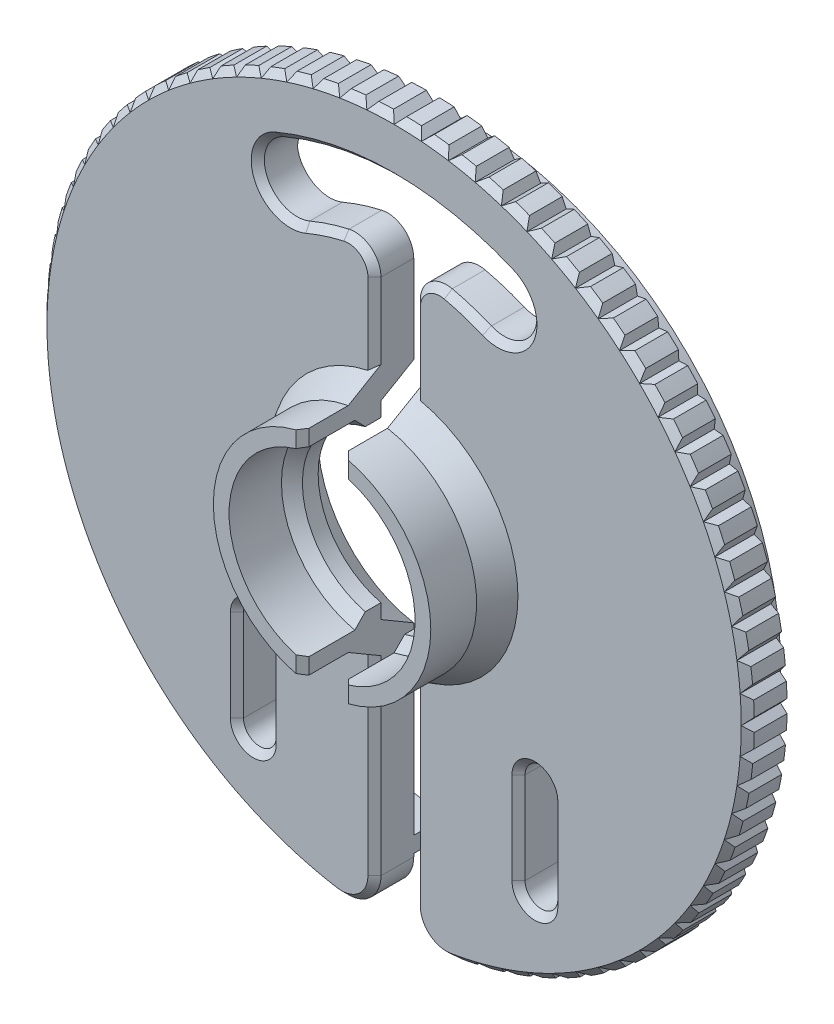
SolidWorks part; units mm, degrees
note: '?' marks a value the reader was unsure of.
ref_plane "Front Plane" through (0, 0, 0) normal (0, 0, 1) x (1, 0, 0)
ref_plane "Top Plane" through (0, 0, 0) normal (0, 1, 0) x (1, 0, 0)
ref_plane "Right Plane" through (0, 0, 0) normal (1, 0, 0) x (0, 0, -1)
sketch "Sketch1" plane through (0, 0, 0) normal (0, 0, 1) x (1, 0, 0)
  circle A0 centre (0, 0) radius 24
  circle A1 centre (0, 0) radius 22.8
  dimension "D1" = 48
  dimension "D2" = 1.2
extrude "coll-lens-ring" add sketch "Sketch1" along normal blind 2.5
ref_axis "Axis1" through (0, 0, 0) along (0, 0, -1)?
sketch "Sketch2" plane through (0, 0, 2.5) normal (0, 0, 1) x (1, 0, 0)
  circle A0 centre (0, 0) radius 27
  circle A1 centre (0, 0) radius 24 construction
  dimension "D1" = 3
extrude "plate" add sketch "Sketch2" along normal blind 3
sketch "Sketch3" plane through (0, 0, 5.5) normal (0, 0, 1) x (1, 0, 0)
  circle A0 centre (0, 0) radius 7.1
  dimension "D1" = 14.2
extrude "lens-hole" cut sketch "Sketch3" against normal through all
sketch "Sketch4" plane through (0, 0, 2.5) normal (0, 0, -1) x (-1, 0, 0)
  circle A0 centre (0, 0) radius 7.1
  circle A1 centre (0, 0) radius 8.3
  circle A2 centre (0, 0) radius 7.1 construction
  dimension "D1" = 1.2
extrude "lens-guide" add sketch "Sketch4" against normal blind 5.5 from surface at -3 starting at face at (7.1, 0, 5.5)
sketch "Sketch5" plane through (0, 0, 11) normal (0, 0, 1) x (1, 0, 0)
  circle A0 centre (0, 0) radius 8.3
  circle A1 centre (0, 0) radius 8.3 construction
  circle A2 centre (0, 0) radius 6.3
  circle A3 centre (0, 0) radius 7.1 construction
  dimension "D1" = 0.8
extrude "lens-stop" add sketch "Sketch5" against normal blind 1 from offset 5 offset against normal yes
chamfer "Chamfer2" distance 2 angle 30 1 edges at (8.3, 0, 5.5)
chamfer "Chamfer3" distance 3 angle 30 1 edges at (7.1, 0, 2.5)
sketch "Sketch6" plane through (0, 0, 2.5) normal (0, 0, -1) x (-1, 0, 0)
  line L0 (0, 0) -> (0, 27) construction
  line L1 (0, 6.05) -> (0, -6.05) construction
  line L2 (-1.5, 6.1188) -> (-1.5, 15.4075)
  line L3 (0, 0) -> (-13.5, 23.3827) construction
  line L4 (-1.5, -26.9583) -> (-1.5, -6.1188)
  line L5 (0, 0) -> (13.5, 23.3827) construction
  line L6 (1.5, -26.9583) -> (1.5, -6.1188)
  line L7 (1.5, 6.1188) -> (1.5, 15.4075)
  circle A0 centre (0, 0) radius 27 construction
  arc A1 (8.8815, 20.999) -> (-8.8815, 20.999) centre (0, 0) ccw
  circle A3 centre (0, 0) radius 6.3 construction
  arc A4 (-6.9338, 16.394) -> (-8.8815, 20.999) centre (-7.9077, 18.6965) cw
  arc A5 (-3.943, 17.3578) -> (-6.9338, 16.394) centre (0, 0) ccw
  arc A6 (-1.5, 15.4075) -> (-3.943, 17.3578) centre (-3.5, 15.4075) ccw
  arc A7 (1.5, 6.1188) -> (-1.5, 6.1188) centre (0, 0) ccw
  arc A8 (-1.5, -6.1188) -> (1.5, -6.1188) centre (0, 0) ccw
  arc A9 (-1.5, -26.9583) -> (1.5, -26.9583) centre (0, 0) ccw
  arc A10 (1.5, 15.4075) -> (3.943, 17.3578) centre (3.5, 15.4075) cw
  arc A11 (3.943, 17.3578) -> (6.9338, 16.394) centre (0, 0) cw
  arc A12 (6.9338, 16.394) -> (8.8815, 20.999) centre (7.9077, 18.6965) ccw
  circle A13 centre (0, 0) radius 22.8 construction
  dimension "D1" = 1.5
  dimension "D2" = 2.5
  dimension "D3" = 2
  dimension "D4" = 30
extrude "flexure-slot" cut sketch "Sketch6" against normal through all both and the other way through all
sketch "Sketch7" plane through (0, 0, 2.5) normal (0, 0, -1) x (-1, 0, 0)
  line L0 (-9.5, -19) -> (-9.5, -12)
  line L1 (-12, -19) -> (-12, -12)
  line L2 (0, 6.05) -> (0, -6.05) construction
  line L3 (12, -19) -> (12, -12)
  line L4 (9.5, -19) -> (9.5, -12)
  arc A0 (-9.5, -19) -> (-12, -19) centre (-10.75, -19) cw
  arc A1 (-12, -12) -> (-9.5, -12) centre (-10.75, -12) cw
  arc A2 (12, -12) -> (9.5, -12) centre (10.75, -12) ccw
  arc A3 (9.5, -19) -> (12, -19) centre (10.75, -19) ccw
  dimension "D1" = 2.5
  dimension "D2" = 7
  dimension "D3" = 9.5
  dimension "D4" = 12
extrude "peg slots" cut sketch "Sketch7" against normal through all
fillet "Fillet1" radius 2 2 edges at (-22.7358, 1.7097, 2.5) (6.1404, -21.9576, 2.5)
fillet "Fillet2" radius 2.5 2 edges at (-1.5, -26.9583, 4) (1.5, -26.9583, 4)
chamfer "Chamfer1" distance 0.5 angle 45 26 edges at (0, 27, 5.5) (-1.5, 12.3712, 5.5) (-2.2522, 16.9705, 5.5) (-5.4597, 16.942, 5.5) (-10.2102, 17.7226, 5.5) (0, 22.8, 5.5) (10.2102, 17.7226, 5.5) (5.4597, 16.942, 5.5) (2.2522, 16.9705, 5.5) (1.5, 12.3712, 5.5) (1.5, -16.7531, 5.5) (-1.5, -16.7531, 5.5) (10.75, -10.75, 5.5) (12, -15.5, 5.5) (9.5, -15.5, 5.5) (10.75, -20.25, 5.5) (-10.75, -10.75, 5.5) (-9.5, -15.5, 5.5) (-12, -15.5, 5.5) (-10.75, -20.25, 5.5) (2.383, -26.0779, 5.5) (-2.383, -26.0779, 5.5) (-1.5, -7.5515, 11) (-1.5, 7.5515, 11) (1.5, -7.5515, 11) (1.5, 7.5515, 11)
chamfer "Chamfer4" distance 1 angle 45 1 edges at (-7.1, 0, 6)
sketch "Sketch8" plane through (0, 0, 6.25) normal (0, 0, 1) x (1, 0, 0)
  line L0 (0, 0) -> (-31.5987, 0) construction
  line L1 (-26.5, 0) -> (-27.3843, -0.9607)
  line L2 (-27.3843, -0.9607) -> (-27.3843, 0.8141)
  line L3 (-27.3843, 0.8141) -> (-26.5, 0)
  line L4 (-27.3753, 1.1909) -> (-27.2361, 2.9601)
  line L5 (-27.2361, 2.9601) -> (-26.4183, 2.0792)
  line L6 (-26.4183, 2.0792) -> (-27.3753, 1.1909)
  line L7 (-27.1975, 3.335) -> (-26.9198, 5.0879)
  line L8 (-26.9198, 5.0879) -> (-26.1737, 4.1455)
  line L9 (-26.1737, 4.1455) -> (-27.1975, 3.335)
  line L10 (-26.852, 5.4586) -> (-26.4377, 7.1844)
  line L11 (-26.4377, 7.1844) -> (-25.7678, 6.1863)
  line L12 (-25.7678, 6.1863) -> (-26.852, 5.4586)
  line L13 (-26.3409, 7.5486) -> (-25.7925, 9.2365)
  line L14 (-25.7925, 9.2365) -> (-25.203, 8.189)
  line L15 (-25.203, 8.189) -> (-26.3409, 7.5486)
  line L16 (-25.6675, 9.592) -> (-24.9883, 11.2317)
  line L17 (-24.9883, 11.2317) -> (-24.4828, 10.1411)
  line L18 (-24.4828, 10.1411) -> (-25.6675, 9.592)
  line L19 (-24.8358, 11.5763) -> (-24.03, 13.1576)
  line L20 (-24.03, 13.1576) -> (-23.6117, 12.0307)
  line L21 (-23.6117, 12.0307) -> (-24.8358, 11.5763)
  line L22 (-23.8509, 13.4892) -> (-22.9236, 15.0024)
  line L23 (-22.9236, 15.0024) -> (-22.595, 13.8462)
  line L24 (-22.595, 13.8462) -> (-23.8509, 13.4892)
  line L25 (-22.7191, 15.3189) -> (-21.6759, 16.7547)
  line L26 (-21.6759, 16.7547) -> (-21.439, 15.5763)
  line L27 (-21.439, 15.5763) -> (-22.7191, 15.3189)
  line L28 (-21.4471, 17.0542) -> (-20.2945, 18.4038)
  line L29 (-20.2945, 18.4038) -> (-20.1508, 17.2104)
  line L30 (-20.1508, 17.2104) -> (-21.4471, 17.0542)
  line L31 (-20.0429, 18.6844) -> (-18.788, 19.9393)
  line L32 (-18.788, 19.9393) -> (-18.7383, 18.7383)
  line L33 (-18.7383, 18.7383) -> (-20.0429, 18.6844)
  line L34 (-18.5152, 20.1993) -> (-17.1657, 21.3519)
  line L35 (-17.1657, 21.3519) -> (-17.2104, 20.1508)
  line L36 (-17.2104, 20.1508) -> (-18.5152, 20.1993)
  line L37 (-16.8733, 21.5897) -> (-15.4375, 22.6329)
  line L38 (-15.4375, 22.6329) -> (-15.5763, 21.439)
  line L39 (-15.5763, 21.439) -> (-16.8733, 21.5897)
  line L40 (-15.1274, 22.8471) -> (-13.6141, 23.7744)
  line L41 (-13.6141, 23.7744) -> (-13.8462, 22.595)
  line L42 (-13.8462, 22.595) -> (-15.1274, 22.8471)
  line L43 (-13.2882, 23.9635) -> (-11.7069, 24.7692)
  line L44 (-11.7069, 24.7692) -> (-12.0307, 23.6117)
  line L45 (-12.0307, 23.6117) -> (-13.2882, 23.9635)
  line L46 (-11.3671, 24.9322) -> (-9.7274, 25.6114)
  line L47 (-9.7274, 25.6114) -> (-10.1411, 24.4828)
  line L48 (-10.1411, 24.4828) -> (-11.3671, 24.9322)
  line L49 (-9.3759, 25.7472) -> (-7.688, 26.2956)
  line L50 (-7.688, 26.2956) -> (-8.189, 25.203)
  line L51 (-8.189, 25.203) -> (-9.3759, 25.7472)
  line L52 (-7.3269, 26.4035) -> (-5.6011, 26.8178)
  line L53 (-5.6011, 26.8178) -> (-6.1863, 25.7678)
  line L54 (-6.1863, 25.7678) -> (-7.3269, 26.4035)
  line L55 (-5.2327, 26.8969) -> (-3.4798, 27.1746)
  line L56 (-3.4798, 27.1746) -> (-4.1455, 26.1737)
  line L57 (-4.1455, 26.1737) -> (-5.2327, 26.8969)
  line L58 (-3.1062, 27.2246) -> (-1.337, 27.3638)
  line L59 (-1.337, 27.3638) -> (-2.0792, 26.4183)
  line L60 (-2.0792, 26.4183) -> (-3.1062, 27.2246)
  line L61 (-0.9607, 27.3843) -> (0.8141, 27.3843)
  line L62 (0.8141, 27.3843) -> (0, 26.5)
  line L63 (0, 26.5) -> (-0.9607, 27.3843)
  line L64 (1.1909, 27.3753) -> (2.9601, 27.2361)
  line L65 (2.9601, 27.2361) -> (2.0792, 26.4183)
  line L66 (2.0792, 26.4183) -> (1.1909, 27.3753)
  line L67 (3.335, 27.1975) -> (5.0879, 26.9198)
  line L68 (5.0879, 26.9198) -> (4.1455, 26.1737)
  line L69 (4.1455, 26.1737) -> (3.335, 27.1975)
  line L70 (5.4586, 26.852) -> (7.1844, 26.4377)
  line L71 (7.1844, 26.4377) -> (6.1863, 25.7678)
  line L72 (6.1863, 25.7678) -> (5.4586, 26.852)
  line L73 (7.5486, 26.3409) -> (9.2365, 25.7925)
  line L74 (9.2365, 25.7925) -> (8.189, 25.203)
  line L75 (8.189, 25.203) -> (7.5486, 26.3409)
  line L76 (9.592, 25.6675) -> (11.2317, 24.9883)
  line L77 (11.2317, 24.9883) -> (10.1411, 24.4828)
  line L78 (10.1411, 24.4828) -> (9.592, 25.6675)
  line L79 (11.5763, 24.8358) -> (13.1576, 24.03)
  line L80 (13.1576, 24.03) -> (12.0307, 23.6117)
  line L81 (12.0307, 23.6117) -> (11.5763, 24.8358)
  line L82 (13.4892, 23.8509) -> (15.0024, 22.9236)
  line L83 (15.0024, 22.9236) -> (13.8462, 22.595)
  line L84 (13.8462, 22.595) -> (13.4892, 23.8509)
  line L85 (15.3189, 22.7191) -> (16.7547, 21.6759)
  line L86 (16.7547, 21.6759) -> (15.5763, 21.439)
  line L87 (15.5763, 21.439) -> (15.3189, 22.7191)
  line L88 (17.0542, 21.4471) -> (18.4038, 20.2945)
  line L89 (18.4038, 20.2945) -> (17.2104, 20.1508)
  line L90 (17.2104, 20.1508) -> (17.0542, 21.4471)
  line L91 (18.6844, 20.0429) -> (19.9393, 18.788)
  line L92 (19.9393, 18.788) -> (18.7383, 18.7383)
  line L93 (18.7383, 18.7383) -> (18.6844, 20.0429)
  line L94 (20.1993, 18.5152) -> (21.3519, 17.1657)
  line L95 (21.3519, 17.1657) -> (20.1508, 17.2104)
  line L96 (20.1508, 17.2104) -> (20.1993, 18.5152)
  line L97 (21.5897, 16.8733) -> (22.6329, 15.4375)
  line L98 (22.6329, 15.4375) -> (21.439, 15.5763)
  line L99 (21.439, 15.5763) -> (21.5897, 16.8733)
  line L100 (22.8471, 15.1274) -> (23.7744, 13.6141)
  line L101 (23.7744, 13.6141) -> (22.595, 13.8462)
  line L102 (22.595, 13.8462) -> (22.8471, 15.1274)
  line L103 (23.9635, 13.2882) -> (24.7692, 11.7069)
  line L104 (24.7692, 11.7069) -> (23.6117, 12.0307)
  line L105 (23.6117, 12.0307) -> (23.9635, 13.2882)
  line L106 (24.9322, 11.3671) -> (25.6114, 9.7274)
  line L107 (25.6114, 9.7274) -> (24.4828, 10.1411)
  line L108 (24.4828, 10.1411) -> (24.9322, 11.3671)
  line L109 (25.7472, 9.3759) -> (26.2956, 7.688)
  line L110 (26.2956, 7.688) -> (25.203, 8.189)
  line L111 (25.203, 8.189) -> (25.7472, 9.3759)
  line L112 (26.4035, 7.3269) -> (26.8178, 5.6011)
  line L113 (26.8178, 5.6011) -> (25.7678, 6.1863)
  line L114 (25.7678, 6.1863) -> (26.4035, 7.3269)
  line L115 (26.8969, 5.2327) -> (27.1746, 3.4798)
  line L116 (27.1746, 3.4798) -> (26.1737, 4.1455)
  line L117 (26.1737, 4.1455) -> (26.8969, 5.2327)
  line L118 (27.2246, 3.1062) -> (27.3638, 1.337)
  line L119 (27.3638, 1.337) -> (26.4183, 2.0792)
  line L120 (26.4183, 2.0792) -> (27.2246, 3.1062)
  line L121 (27.3843, 0.9607) -> (27.3843, -0.8141)
  line L122 (27.3843, -0.8141) -> (26.5, 0)
  line L123 (26.5, 0) -> (27.3843, 0.9607)
  line L124 (27.3753, -1.1909) -> (27.2361, -2.9601)
  line L125 (27.2361, -2.9601) -> (26.4183, -2.0792)
  line L126 (26.4183, -2.0792) -> (27.3753, -1.1909)
  line L127 (27.1975, -3.335) -> (26.9198, -5.0879)
  line L128 (26.9198, -5.0879) -> (26.1737, -4.1455)
  line L129 (26.1737, -4.1455) -> (27.1975, -3.335)
  line L130 (26.852, -5.4586) -> (26.4377, -7.1844)
  line L131 (26.4377, -7.1844) -> (25.7678, -6.1863)
  line L132 (25.7678, -6.1863) -> (26.852, -5.4586)
  line L133 (26.3409, -7.5486) -> (25.7925, -9.2365)
  line L134 (25.7925, -9.2365) -> (25.203, -8.189)
  line L135 (25.203, -8.189) -> (26.3409, -7.5486)
  line L136 (25.6675, -9.592) -> (24.9883, -11.2317)
  line L137 (24.9883, -11.2317) -> (24.4828, -10.1411)
  line L138 (24.4828, -10.1411) -> (25.6675, -9.592)
  line L139 (24.8358, -11.5763) -> (24.03, -13.1576)
  line L140 (24.03, -13.1576) -> (23.6117, -12.0307)
  line L141 (23.6117, -12.0307) -> (24.8358, -11.5763)
  line L142 (23.8509, -13.4892) -> (22.9236, -15.0024)
  line L143 (22.9236, -15.0024) -> (22.595, -13.8462)
  line L144 (22.595, -13.8462) -> (23.8509, -13.4892)
  line L145 (22.7191, -15.3189) -> (21.6759, -16.7547)
  line L146 (21.6759, -16.7547) -> (21.439, -15.5763)
  line L147 (21.439, -15.5763) -> (22.7191, -15.3189)
  line L148 (21.4471, -17.0542) -> (20.2945, -18.4038)
  line L149 (20.2945, -18.4038) -> (20.1508, -17.2104)
  line L150 (20.1508, -17.2104) -> (21.4471, -17.0542)
  line L151 (20.0429, -18.6844) -> (18.788, -19.9393)
  line L152 (18.788, -19.9393) -> (18.7383, -18.7383)
  line L153 (18.7383, -18.7383) -> (20.0429, -18.6844)
  line L154 (18.5152, -20.1993) -> (17.1657, -21.3519)
  line L155 (17.1657, -21.3519) -> (17.2104, -20.1508)
  line L156 (17.2104, -20.1508) -> (18.5152, -20.1993)
  line L157 (16.8733, -21.5897) -> (15.4375, -22.6329)
  line L158 (15.4375, -22.6329) -> (15.5763, -21.439)
  line L159 (15.5763, -21.439) -> (16.8733, -21.5897)
  line L160 (15.1274, -22.8471) -> (13.6141, -23.7744)
  line L161 (13.6141, -23.7744) -> (13.8462, -22.595)
  line L162 (13.8462, -22.595) -> (15.1274, -22.8471)
  line L163 (13.2882, -23.9635) -> (11.7069, -24.7692)
  line L164 (11.7069, -24.7692) -> (12.0307, -23.6117)
  line L165 (12.0307, -23.6117) -> (13.2882, -23.9635)
  line L166 (11.3671, -24.9322) -> (9.7274, -25.6114)
  line L167 (9.7274, -25.6114) -> (10.1411, -24.4828)
  line L168 (10.1411, -24.4828) -> (11.3671, -24.9322)
  line L169 (9.3759, -25.7472) -> (7.688, -26.2956)
  line L170 (7.688, -26.2956) -> (8.189, -25.203)
  line L171 (8.189, -25.203) -> (9.3759, -25.7472)
  line L172 (7.3269, -26.4035) -> (5.6011, -26.8178)
  line L173 (5.6011, -26.8178) -> (6.1863, -25.7678)
  line L174 (6.1863, -25.7678) -> (7.3269, -26.4035)
  line L175 (5.2327, -26.8969) -> (3.4798, -27.1746)
  line L176 (3.4798, -27.1746) -> (4.1455, -26.1737)
  line L177 (4.1455, -26.1737) -> (5.2327, -26.8969)
  line L178 (3.1062, -27.2246) -> (1.337, -27.3638)
  line L179 (1.337, -27.3638) -> (2.0792, -26.4183)
  line L180 (2.0792, -26.4183) -> (3.1062, -27.2246)
  line L181 (0.9607, -27.3843) -> (-0.8141, -27.3843)
  line L182 (-0.8141, -27.3843) -> (0, -26.5)
  line L183 (0, -26.5) -> (0.9607, -27.3843)
  line L184 (-1.1909, -27.3753) -> (-2.9601, -27.2361)
  line L185 (-2.9601, -27.2361) -> (-2.0792, -26.4183)
  line L186 (-2.0792, -26.4183) -> (-1.1909, -27.3753)
  line L187 (-3.335, -27.1975) -> (-5.0879, -26.9198)
  line L188 (-5.0879, -26.9198) -> (-4.1455, -26.1737)
  line L189 (-4.1455, -26.1737) -> (-3.335, -27.1975)
  line L190 (-5.4586, -26.852) -> (-7.1844, -26.4377)
  line L191 (-7.1844, -26.4377) -> (-6.1863, -25.7678)
  line L192 (-6.1863, -25.7678) -> (-5.4586, -26.852)
  line L193 (-7.5486, -26.3409) -> (-9.2365, -25.7925)
  line L194 (-9.2365, -25.7925) -> (-8.189, -25.203)
  line L195 (-8.189, -25.203) -> (-7.5486, -26.3409)
  line L196 (-9.592, -25.6675) -> (-11.2317, -24.9883)
  line L197 (-11.2317, -24.9883) -> (-10.1411, -24.4828)
  line L198 (-10.1411, -24.4828) -> (-9.592, -25.6675)
  line L199 (-11.5763, -24.8358) -> (-13.1576, -24.03)
  line L200 (-13.1576, -24.03) -> (-12.0307, -23.6117)
  line L201 (-12.0307, -23.6117) -> (-11.5763, -24.8358)
  line L202 (-13.4892, -23.8509) -> (-15.0024, -22.9236)
  line L203 (-15.0024, -22.9236) -> (-13.8462, -22.595)
  line L204 (-13.8462, -22.595) -> (-13.4892, -23.8509)
  line L205 (-15.3189, -22.7191) -> (-16.7547, -21.6759)
  line L206 (-16.7547, -21.6759) -> (-15.5763, -21.439)
  line L207 (-15.5763, -21.439) -> (-15.3189, -22.7191)
  line L208 (-17.0542, -21.4471) -> (-18.4038, -20.2945)
  line L209 (-18.4038, -20.2945) -> (-17.2104, -20.1508)
  line L210 (-17.2104, -20.1508) -> (-17.0542, -21.4471)
  line L211 (-18.6844, -20.0429) -> (-19.9393, -18.788)
  line L212 (-19.9393, -18.788) -> (-18.7383, -18.7383)
  line L213 (-18.7383, -18.7383) -> (-18.6844, -20.0429)
  line L214 (-20.1993, -18.5152) -> (-21.3519, -17.1657)
  line L215 (-21.3519, -17.1657) -> (-20.1508, -17.2104)
  line L216 (-20.1508, -17.2104) -> (-20.1993, -18.5152)
  line L217 (-21.5897, -16.8733) -> (-22.6329, -15.4375)
  line L218 (-22.6329, -15.4375) -> (-21.439, -15.5763)
  line L219 (-21.439, -15.5763) -> (-21.5897, -16.8733)
  line L220 (-22.8471, -15.1274) -> (-23.7744, -13.6141)
  line L221 (-23.7744, -13.6141) -> (-22.595, -13.8462)
  line L222 (-22.595, -13.8462) -> (-22.8471, -15.1274)
  line L223 (-23.9635, -13.2882) -> (-24.7692, -11.7069)
  line L224 (-24.7692, -11.7069) -> (-23.6117, -12.0307)
  line L225 (-23.6117, -12.0307) -> (-23.9635, -13.2882)
  line L226 (-24.9322, -11.3671) -> (-25.6114, -9.7274)
  line L227 (-25.6114, -9.7274) -> (-24.4828, -10.1411)
  line L228 (-24.4828, -10.1411) -> (-24.9322, -11.3671)
  line L229 (-25.7472, -9.3759) -> (-26.2956, -7.688)
  line L230 (-26.2956, -7.688) -> (-25.203, -8.189)
  line L231 (-25.203, -8.189) -> (-25.7472, -9.3759)
  line L232 (-26.4035, -7.3269) -> (-26.8178, -5.6011)
  line L233 (-26.8178, -5.6011) -> (-25.7678, -6.1863)
  line L234 (-25.7678, -6.1863) -> (-26.4035, -7.3269)
  line L235 (-26.8969, -5.2327) -> (-27.1746, -3.4798)
  line L236 (-27.1746, -3.4798) -> (-26.1737, -4.1455)
  line L237 (-26.1737, -4.1455) -> (-26.8969, -5.2327)
  line L238 (-27.2246, -3.1062) -> (-27.3638, -1.337)
  line L239 (-27.3638, -1.337) -> (-26.4183, -2.0792)
  line L240 (-26.4183, -2.0792) -> (-27.2246, -3.1062)
  arc A0 (4.3265, -26.1444) -> (-4.3265, -26.1444) centre (0, 0) ccw construction
  point P250 (0, 0)
  dimension "D1" = 80
extrude "edge knurl" cut sketch "Sketch8" against normal through all
